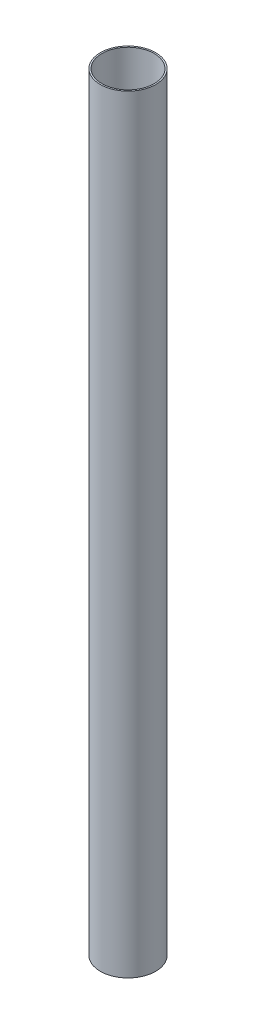
SolidWorks part; units mm, degrees
material "6063-T6"
ref_plane "Front Plane" through (0, 0, 0) normal (0, 0, 1) x (1, 0, 0)
ref_plane "Top Plane" through (0, 0, 0) normal (0, 1, 0) x (1, 0, 0)
ref_plane "Right Plane" through (0, 0, 0) normal (1, 0, 0) x (0, 0, -1)
sketch "Sketch1" plane through (0, 0, 0) normal (0, 0, 1) x (1, 0, 0)
  line L0 (0, 0) -> (0, 45.6531) construction
  line L1 (25.5143, 85.0355) -> (26.9875, 85.0355)
  line L2 (25.5143, 85.0355) -> (25.5143, -664.2645)
  line L3 (25.5143, -664.2645) -> (26.9875, -664.2645)
  line L4 (26.9875, 85.0355) -> (26.9875, -664.2645)
revolve "Revolve1" add sketch "Sketch1" angle 360 about L0
